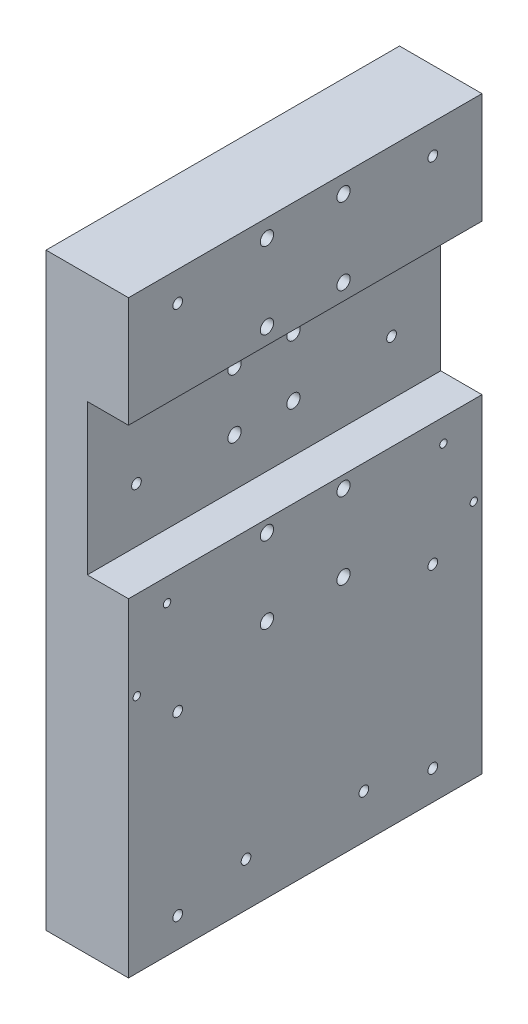
SolidWorks part; units mm, degrees
ref_plane "Front Plane" through (0, 0, 0) normal (0, 0, 1) x (1, 0, 0)
ref_plane "Top Plane" through (0, 0, 0) normal (0, 1, 0) x (1, 0, 0)
ref_plane "Right Plane" through (0, 0, 0) normal (1, 0, 0) x (0, 0, -1)
sketch "Sketch1" plane through (0, 0, 0) normal (0, 0, 1) x (1, 0, 0)
  line L0 (0, 0) -> (0, 200)
  line L1 (0, 200) -> (28, 200)
  line L2 (28, 200) -> (28, 162.5)
  line L3 (14, 162.5) -> (14, 111.5)
  line L4 (14, 162.5) -> (28, 162.5)
  line L5 (14, 111.5) -> (28, 111.5)
  line L6 (28, 111.5) -> (28, 0)
  line L7 (28, 0) -> (0, 0)
  line L8 (-49.525, 137) -> (95.9642, 137) construction
  point P12 (14, 137)
  dimension "D1" = 200
  dimension "D2" = 25.5
  dimension "D4" = 28
  dimension "D6" = 63
extrude "Boss-Extrude1" add sketch "Sketch1" along normal blind 120 contours L0 L1 L2 L4 L3 L5 L6 L7
sketch "Sketch2" plane through (0, 0, 0) normal (-1, 0, 0) x (0, 0, 1)
  line L0 (60, 200) -> (60, 0) construction
  line L1 (120, 200) -> (0, 200) construction
  line L2 (120, 0) -> (0, 0) construction
  point P6 (73, 194)
  point P7 (73, 168)
  point P8 (70, 147.7)
  point P9 (70, 127.7)
  point P10 (73, 107.4)
  point P11 (73, 81.4)
  point P12 (47, 81.4)
  point P13 (47, 107.4)
  point P14 (50, 127.7)
  point P15 (50, 147.7)
  point P16 (47, 168)
  point P17 (47, 194)
  dimension "D1" = 6
  dimension "D2" = 26
  dimension "D3" = 46.3
  dimension "D4" = 20
  dimension "D5" = 20.3
  dimension "D6" = 26
  dimension "D7" = 13
  dimension "D8" = 10
hole_wizard "CBORE for M4 SHCS4" positions "3DSketch2" profile "Sketch4" counterbore size "M4" standard "ANSI Metric" end condition through all
sketch3d "3DSketch2"
  point P0 (0, 194, 73)
  point P3 (0, 168, 73)
  point P6 (0, 147.7, 70)
  point P9 (0, 127.7, 70)
  point P12 (0, 107.4, 73)
  point P15 (0, 81.4, 73)
  point P18 (0, 81.4, 47)
  point P21 (0, 107.4, 47)
  point P24 (0, 127.7, 50)
  point P27 (0, 147.7, 50)
  point P30 (0, 168, 47)
  point P33 (0, 194, 47)
sketch "Sketch4" plane through (0, 194, 73) normal (0, 1, 0) x (0, 0, 1)
  line L0 (0, 0) -> (0, 28)
  line L1 (0, 28) -> (2.25, 28)
  line L3 (2.25, 28) -> (2.25, 4)
  line L4 (2.25, 4) -> (4, 4)
  line L5 (4, 4) -> (4, 0)
  line L7 (4, 0) -> (0, 0)
  line L11 (0, -6.35) -> (0, 107.95) construction
  dimension "Thru Hole Dia." = 4.5
  dimension "Thru Hole Depth" = 28
  dimension "C'Bore Dia." = 8
  dimension "C'Bore Depth" = 4
sketch "Sketch5" plane through (0, 0, 0) normal (-1, 0, 0) x (0, 0, 1)
  line L0 (16.7, 200) -> (16.7, 0) construction
  line L1 (120, 200) -> (0, 200) construction
  line L2 (120, 0) -> (0, 0) construction
  line L3 (60, 200) -> (60, 0) construction
  line L4 (60, 200) -> (60, 0) construction
  line L5 (103.3, 200) -> (103.3, 0) construction
  point P12 (16.7, 190)
  point P13 (103.3, 10)
  point P14 (16.7, 130)
  point P15 (16.7, 70)
  point P16 (16.7, 10)
  point P17 (103.3, 70)
  point P18 (103.3, 130)
  point P19 (103.3, 190)
  dimension "D1" = 43.3
  dimension "D2" = 10
  dimension "D3" = 4
hole_wizard "M4 Tapped Hole1" positions "3DSketch3" profile "Sketch6" tap size "M4" standard "ISO" end condition through all
sketch3d "3DSketch3"
  point P0 (0, 190, 16.7)
  point P3 (0, 130, 16.7)
  point P6 (0, 70, 16.7)
  point P9 (0, 10, 16.7)
  point P12 (0, 10, 103.3)
  point P15 (0, 70, 103.3)
  point P18 (0, 130, 103.3)
  point P21 (0, 190, 103.3)
sketch "Sketch6" plane through (0, 190, 16.7) normal (0, 1, 0) x (0, 0, 1)
  line L0 (0, 0) -> (0, 28)
  line L1 (0, 28) -> (1.65, 28)
  line L2 (1.65, 28) -> (1.65, 0)
  line L5 (1.65, 0) -> (0, 0)
  line L11 (0, -6.35) -> (0, 107.95) construction
  dimension "Thread Major Dia." = 3.3
  dimension "Thru Tap Drill Depth" = 28
ref_plane "Plane1" through (0, 0, 60) normal (0, 0, -1) x (-1, 0, 0)
sketch "Sketch7" plane through (0, 0, 0) normal (0, -1, 0) x (1, 0, 0)
  line L0 (14, 120) -> (14, 0) construction
  line L1 (28, 120) -> (0, 120) construction
  line L2 (28, 0) -> (0, 0) construction
  line L3 (28, 60) -> (0, 60) construction
  line L4 (28, 120) -> (28, 0) construction
  line L5 (0, 120) -> (0, 0) construction
  point P12 (14, 60)
  point P13 (14, 90)
  point P14 (14, 30)
  dimension "D1" = 30
hole_wizard "M5 Tapped Hole1" positions "3DSketch4" profile "Sketch8" tap size "M5" standard "ISO"
sketch3d "3DSketch4"
  point P0 (14, 0, 90)
  point P3 (14, 0, 60)
  point P6 (14, 0, 30)
sketch "Sketch8" plane through (14, 0, 90) normal (1, 0, 0) x (0, 0, -1)
  line L0 (0, 0) -> (0, 18.6618)
  line L1 (0, 18.6618) -> (2.1, 17.4)
  line L2 (2.1, 17.4) -> (2.1, 0)
  line L5 (2.1, 0) -> (0, 0)
  line L10 (0, 18.6618) -> (-2.1, 17.4) construction
  line L11 (0, -6.35) -> (0, 107.95) construction
  dimension "Tap Drill Dia." = 4.2
  dimension "Tap Drill Depth" = 17.4
  dimension "Drill Angle" = 118
sketch "Sketch9" plane through (28, 0, 0) normal (1, 0, 0) x (0, 0, -1)
  line L0 (-40.1, 23.78) -> (-40.1, 0) construction
  line L1 (-80.1, 23.78) -> (-80.1, 0) construction
  line L8 (-120, 0) -> (0, 0) construction
  line L11 (-120, 0) -> (0, 0) construction
  point P8 (-40.1, 15)
  point P9 (-80.1, 15)
  dimension "D1" = 15
hole_wizard "M4 Tapped Hole2" positions "3DSketch5" profile "Sketch10" tap size "M4" standard "ISO" end condition through all
sketch3d "3DSketch5"
  point P0 (28, 15, 80.1)
  point P3 (28, 15, 40.1)
sketch "Sketch10" plane through (28, 15, 80.1) normal (0, 1, 0) x (0, 0, -1)
  line L0 (0, 0) -> (0, 28)
  line L1 (0, 28) -> (1.65, 28)
  line L2 (1.65, 28) -> (1.65, 0)
  line L5 (1.65, 0) -> (0, 0)
  line L11 (0, -6.35) -> (0, 107.95) construction
  dimension "Thread Major Dia." = 3.3
  dimension "Thru Tap Drill Depth" = 28
sketch "Sketch16" plane through (28, 0, 0) normal (1, 0, 0) x (0, 0, -1)
  line L0 (-60, 200) -> (-60, 0) construction
  point P0 (-2.8, 81.4604)
  point P1 (-13.1, 103.6604)
  point P8 (-117.2, 81.4604)
  point P9 (-106.9, 103.6604)
hole_wizard "M3 Tapped Hole2" positions "3DSketch12" profile "Sketch18" tap size "M3" standard "ISO"
sketch3d "3DSketch12"
  point P0 (28, 103.6604, 106.9)
  point P3 (28, 81.4604, 117.2)
  point P6 (28, 103.6604, 13.1)
  point P9 (28, 81.4604, 2.8)
sketch "Sketch18" plane through (28, 103.6604, 106.9) normal (0, 1, 0) x (0, 0, -1)
  line L0 (0, 0) -> (0, 12.2511)
  line L1 (0, 12.2511) -> (1.25, 11.5)
  line L2 (1.25, 11.5) -> (1.25, 0)
  line L5 (1.25, 0) -> (0, 0)
  line L10 (0, 12.2511) -> (-1.25, 11.5) construction
  line L11 (0, -6.35) -> (0, 107.95) construction
  dimension "Tap Drill Dia." = 2.5
  dimension "Tap Drill Depth" = 11.5
  dimension "Drill Angle" = 118
